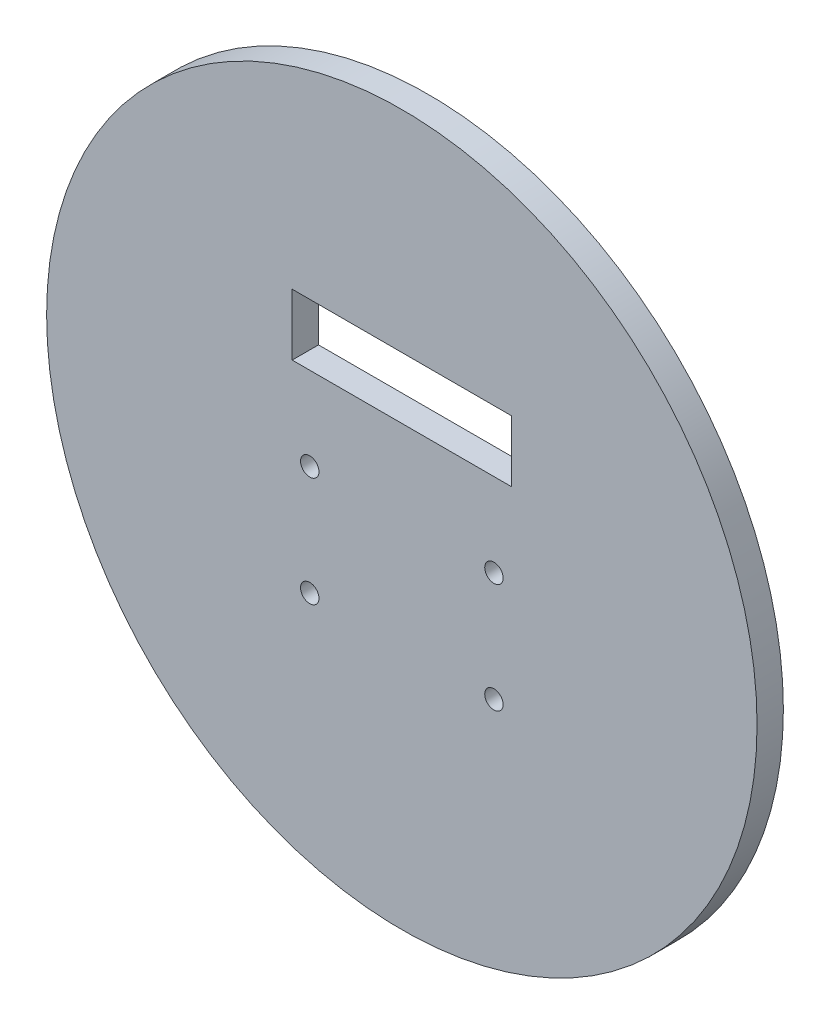
SolidWorks part; units mm, degrees
ref_plane "Plan de face" through (0, 0, 0) normal (0, 0, 1) x (1, 0, 0)
ref_plane "Plan de dessus" through (0, 0, 0) normal (0, 1, 0) x (1, 0, 0)
ref_plane "Plan de droite" through (0, 0, 0) normal (1, 0, 0) x (0, 0, -1)
sketch "Esquisse1" plane through (0, 0, 0) normal (0, 0, 1) x (1, 0, 0)
  line L0 (0, 0) -> (-10.5, 0) construction
  line L1 (-10.5, 0) -> (-10.5, -12.5) construction
  line L2 (-10.5, -12.5) -> (10.5, -12.5) construction
  line L3 (10.5, -12.5) -> (10.5, 0) construction
  line L4 (10.5, 0) -> (0, 0) construction
  circle A0 centre (0, 0) radius 40.5
  circle A1 centre (-10.5, -12.5) radius 1.05
  circle A2 centre (10.5, -12.5) radius 1.05
  circle A3 centre (-10.5, 0) radius 1.05
  circle A4 centre (10.5, 0) radius 1.05
  dimension "D1" = 81
  dimension "D6" = 2.1
  dimension "D7" = 2.1
  dimension "D8" = 2.1
  dimension "D9" = 2.1
  dimension "D2" = 10.5
  dimension "D3" = 10.5
  dimension "D4" = 12.5
  dimension "D5" = 21
extrude "Boss.-Extru.1" add sketch "Esquisse1" along normal blind 3
sketch "Esquisse2" plane through (0, 0, 0) normal (0, 0, 1) x (1, 0, 0)
  line L1 (12.5, 9.5) -> (-12.5, 9.5)
  line L2 (12.5, 9.5) -> (12.5, -14.5)
  line L3 (12.5, -14.5) -> (-12.5, -14.5)
  line L4 (-12.5, 9.5) -> (-12.5, -14.5)
  line L6 (0, 4) -> (0, -14.5)
  line L7 (12.5, 9.5) -> (-12.5, 9.5)
  line L8 (12.5, 9.5) -> (12.5, 16.5)
  line L9 (12.5, 16.5) -> (-12.5, 16.5)
  line L10 (-12.5, 9.5) -> (-12.5, 16.5)
  line L11 (12.5, 9.5) -> (-12.5, 9.5)
  line L12 (12.5, 9.5) -> (12.5, 4)
  line L14 (-12.5, 9.5) -> (-12.5, 4)
  line L15 (12.5, 9.5) -> (-12.5, 9.5)
  line L16 (12.5, 9.5) -> (12.5, 4)
  line L17 (12.5, 4) -> (-12.5, 4)
  line L18 (-12.5, 9.5) -> (-12.5, 4)
  circle A0 centre (10.5, -12.5) radius 1.05 construction
  dimension "D1" = 24
  dimension "D2" = 25
  dimension "D3" = 2
  dimension "D4" = 2
  dimension "D5" = 25
  dimension "D6" = 7
  dimension "D7" = 18.5
extrude "Enlèv. mat.-Extru.4" cut sketch "Esquisse2" along normal blind 14 contours L10 L1 L8 L9 region at (0, 13, 0)
extrude "Boss.-Extru.6" add sketch "Esquisse2<7>" against normal blind 2 contours L17 L2 L1 L4 region at (0, 6.75, 0)
sketch "Esquisse2<7>" plane through (0, 0, 0) normal (0, 0, 1) x (1, 0, 0) same geometry as "Esquisse2"
extrude "Enlèv. mat.-Extru.5" cut sketch "Esquisse2<8>" against normal blind 2 contours L17 L2 L1 L4 region at (0, 6.75, 0)
sketch "Esquisse2<8>" plane through (0, 0, 0) normal (0, 0, 1) x (1, 0, 0) same geometry as "Esquisse2"
extrude "Boss.-Extru.7" add sketch "Esquisse2<9>" against normal blind 2 contours L2 L17 L6 L3 | L6 L17 L4 L3 region at (6.25, -5.25, 0) region at (-6.25, -5.25, 0)
sketch "Esquisse2<9>" plane through (0, 0, 0) normal (0, 0, 1) x (1, 0, 0) same geometry as "Esquisse2"
sketch "Esquisse7" plane through (0, 0, 0) normal (0, 0, 1) x (1, 0, 0)
  circle A0 centre (-10.5, 0) radius 1.05
  circle A1 centre (-10.5, -12.5) radius 1.05
  circle A2 centre (10.5, 0) radius 1.05
  circle A3 centre (10.5, -12.5) radius 1.05
  dimension "D1" = 2.1
  dimension "D2" = 2.1
  dimension "D3" = 2.1
  dimension "D4" = 2.1
extrude "Enlèv. mat.-Extru.6" cut sketch "Esquisse7" against normal through all both and the other way through all
